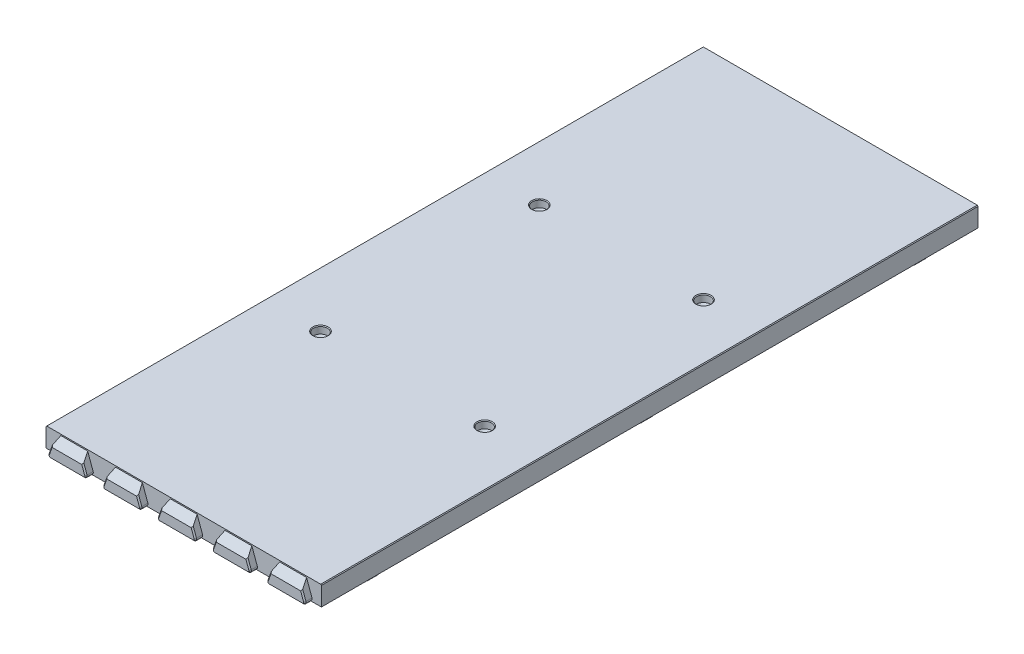
SolidWorks part; units mm, degrees
ref_plane "Front Plane" through (0, 0, 0) normal (0, 0, 1) x (1, 0, 0)
ref_plane "Top Plane" through (0, 0, 0) normal (0, 1, 0) x (1, 0, 0)
ref_plane "Right Plane" through (0, 0, 0) normal (1, 0, 0) x (0, 0, -1)
sketch "Sketch1" plane through (0, 0, 0) normal (0, 0, 1) x (1, 0, 0)
  line L0 (0, 0) -> (0, 8) construction
  line L1 (-56.625, 0) -> (0, 0) construction
  line L2 (-56.625, 0) -> (-56.625, 8)
  line L3 (-56.625, 8) -> (56.625, 8)
  line L5 (-56.625, 0) -> (-54.625, 0)
  line L6 (-54.625, 0) -> (-54.625, 6)
  line L7 (-54.625, 6) -> (54.625, 6)
  line L9 (54.625, 0) -> (54.625, 6)
  line L10 (56.625, 0) -> (54.625, 0)
  line L11 (56.625, 0) -> (56.625, 8)
  point P8 (0, 6)
  dimension "D2" = 6
  dimension "D1" = 56.625
  dimension "D3" = 2
  dimension "D4" = 2
extrude "Boss-Extrude1" add sketch "Sketch1" against normal blind 135
sketch "Sketch7" plane through (0, 0, 0) normal (0, 0, 1) x (1, 0, 0)
  line L2 (-54.625, 0) -> (54.625, 0)
  line L13 (-54.625, 0) -> (-54.625, 6)
  line L15 (-54.625, 6) -> (54.625, 6)
  line L16 (54.625, 0) -> (54.625, 6)
  line M3 (-54.625, 0) -> (-54.625, 6)
  line M4 (-54.625, 6) -> (54.625, 6)
  line M5 (54.625, 6) -> (54.625, 0)
extrude "Boss-Extrude7" add sketch "Sketch7" against normal blind 1 contours M4 M3 | M5 region at (0, 3, 0)
sketch "Sketch2" plane through (0, 0, 0) normal (0, 0, 1) x (1, 0, 0)
  line L14 (39.6618, 8) -> (36.75, 0)
  line L15 (56.625, 8) -> (-56.625, 8) construction
  line L16 (-56.625, 0) -> (56.625, 0) construction
  line L17 (36.75, 0) -> (53.25, 0)
  line L18 (39.6618, 8) -> (50.3382, 8)
  line L19 (-56.625, 0) -> (56.625, 0) construction
  line L21 (50.3382, 8) -> (53.25, 0)
  line L24 (33.75, 0) -> (33.75, 8) construction
  line L27 (17.1618, 8) -> (14.25, 0)
  line L28 (17.1618, 8) -> (27.8382, 8)
  line L29 (14.25, 0) -> (30.75, 0)
  line L30 (27.8382, 8) -> (30.75, 0)
  line L31 (-5.3382, 8) -> (-8.25, 0)
  line L32 (-5.3382, 8) -> (5.3382, 8)
  line L33 (-8.25, 0) -> (8.25, 0)
  line L34 (5.3382, 8) -> (8.25, 0)
  line L35 (-27.8382, 8) -> (-30.75, 0)
  line L36 (-27.8382, 8) -> (-17.1618, 8)
  line L37 (-30.75, 0) -> (-14.25, 0)
  line L38 (-17.1618, 8) -> (-14.25, 0)
  line L39 (39.6618, 8) -> (17.1618, 8) construction
  line L40 (56.25, 8) -> (56.25, 0) construction
  line L41 (56.625, 0) -> (56.625, 8) construction
  line L42 (-56.25, 8) -> (-56.25, 0) construction
  line L43 (-56.625, 8) -> (-56.625, 0) construction
  line L44 (-50.3382, 8) -> (-53.25, 0)
  line L45 (-50.3382, 8) -> (-39.6618, 8)
  line L46 (-53.25, 0) -> (-36.75, 0)
  line L47 (-39.6618, 8) -> (-36.75, 0)
  point P22 (45, 8)
  point P23 (22.5, 8)
  dimension "D1" = 70
  dimension "D2" = 0.375
  dimension "D3" = 3
  dimension "D4" = 3
  dimension "D5" = 70
  dimension "D7" = 22.5
  dimension "D8" = 22.5
  dimension "D9" = 0.375
  dimension "D10" = 25.5
  dimension "D11" = 8
  dimension "D6" = 5
extrude "Boss-Extrude4" add sketch "Sketch2" along normal blind 3
sketch "Sketch8" plane through (0, 0, 0) normal (0, -1, 0) x (1, 0, 0)
  line L0 (-56.625, -22.5) -> (56.625, -22.5) construction
  line L2 (56.625, -135) -> (56.625, 0) construction
  line L3 (-56.625, 0) -> (-53.25, 0) construction
  line L4 (-55.25, -24.9559) -> (-55.25, -20.0441)
  line L5 (-55.25, -20.0441) -> (-51.25, -21.5)
  line L6 (-51.25, -21.5) -> (-51.25, -23.5)
  line L7 (-55.25, -135) -> (-55.25, -132.5441)
  line L8 (-55.25, -132.5441) -> (-51.25, -134)
  line L9 (-51.25, -134) -> (-51.25, -135)
  line L10 (-54.625, -135) -> (54.625, -135) construction
  line L11 (-51.25, -135) -> (-55.25, -135)
  line L12 (-55.25, -24.9559) -> (-51.25, -23.5)
  line L13 (0, -135) -> (0, 0) construction
  line L23 (-56.625, -135) -> (-56.625, 0) construction
  line L24 (55.25, -24.9559) -> (51.25, -23.5)
  line L25 (51.25, -21.5) -> (51.25, -23.5)
  line L26 (55.25, -20.0441) -> (51.25, -21.5)
  line L27 (55.25, -24.9559) -> (55.25, -20.0441)
  line L28 (-56.625, -135) -> (-54.625, -135) construction
  line L29 (51.25, -135) -> (55.25, -135)
  line L30 (51.25, -134) -> (51.25, -135)
  line L31 (55.25, -132.5441) -> (51.25, -134)
  line L32 (55.25, -135) -> (55.25, -132.5441)
  point P19 (-51.25, -22.5)
  point P32 (51.25, -22.5)
  dimension "D1" = 22.5
  dimension "D3" = 70
  dimension "D4" = 4
  dimension "D5" = 1.375
  dimension "D6" = 4
  dimension "D7" = 70
  dimension "D8" = 1
  dimension "D9" = 1
extrude "Boss-Extrude8" add sketch "Sketch8" against normal up to next and the other way blind 2
chamfer "Chamfer4" distance 0.5 angle 45 14 edges at (-51.25, -2, -134.5) (-53.25, -2, -133.2721) (-55.25, -2, -133.7721) (-53.25, -2, -24.2279) (-51.25, -2, -22.5) (-53.25, -2, -20.7721) (51.25, -2, -22.5) (53.25, -2, -24.2279) (53.25, -2, -20.7721) (55.25, -2, -22.5) (51.25, -2, -134.5) (55.25, -2, -133.7721) (53.25, -2, -133.2721) (-55.25, -2, -22.5)
fillet "Fillet4" radius 1 10 edges at (53.25, 0, 1.5) (36.75, 0, 1.5) (30.75, 0, 1.5) (14.25, 0, 1.5) (8.25, 0, 1.5) (-8.25, 0, 1.5) (-14.25, 0, 1.5) (-30.75, 0, 1.5) (-36.75, 0, 1.5) (-53.25, 0, 1.5)
chamfer "Chamfer6" distance 0.5 angle 45 25 edges at (38.4501, 4.671, 3) (51.5499, 4.671, 3) (45, 0, 3) (-29.0499, 4.671, 3) (-22.5, 0, 3) (-15.9501, 4.671, 3) (-6.5499, 4.671, 3) (0, 0, 3) (6.5499, 4.671, 3) (15.9501, 4.671, 3) (29.0499, 4.671, 3) (22.5, 0, 3) (-51.5499, 4.671, 3) (-38.4501, 4.671, 3) (-45, 0, 3) (-52.641, 0.4264, 3) (-37.359, 0.4264, 3) (-30.141, 0.4264, 3) (-14.859, 0.4264, 3) (-7.641, 0.4264, 3) (7.641, 0.4264, 3) (14.859, 0.4264, 3) (30.141, 0.4264, 3) (37.359, 0.4264, 3) (52.641, 0.4264, 3)
fillet "Fillet2" radius 2 23 edges at (0, 6, -1) (-54.625, 3, -132.7716) (-52.9375, 6, -133.3858) (-51.25, 6, -134.5) (-54.625, 3, -1) (-52.9375, 6, -20.8858) (-54.625, 3, -20.2716) (-54.625, 6, -78.75) (-51.25, 6, -22.5) (-52.9375, 6, -24.1142) (-54.625, 3, -24.7284) (54.625, 6, -10.6358) (54.625, 3, -1) (-54.625, 6, -10.6358) (54.625, 3, -24.7284) (54.625, 3, -20.2716) (54.625, 3, -132.7716) (51.25, 6, -134.5) (52.9375, 6, -133.3858) (52.9375, 6, -20.8858) (51.25, 6, -22.5) (54.625, 6, -78.75) (52.9375, 6, -24.1142)
mirror "Mirror2" about plane through (0, 0, -135) normal (0, 0, 1) of "Fillet4", "Boss-Extrude1", "Boss-Extrude7", "Boss-Extrude4", "Boss-Extrude8", "Chamfer4", "Fillet2", "Chamfer6"
sketch "Sketch9" plane through (0, 0, 0) normal (0, 1, 0) x (1, 0, 0)
  line L16 (0, 135) -> (0, 0) construction
  line L17 (-56.625, 135) -> (56.625, 135) construction
  line L18 (-56.625, 137.9563) -> (-56.625, 132.0437) construction
  line L20 (56.625, 270) -> (56.625, 0) construction
  circle A0 centre (-33.75, 90) radius 5
  circle A4 centre (33.75, 90) radius 5
  circle A5 centre (33.75, 180) radius 5
  circle A6 centre (-33.75, 180) radius 5
  point P23 (0, 135)
  point P24 (0, 135)
  dimension "D3" = 10
  dimension "D1" = 33.75
  dimension "D2" = 45
extrude "Boss-Extrude9" add sketch "Sketch9" along normal up to next
fillet "Fillet3" radius 3 4 edges at (-33.75, 6, -95) (33.75, 6, -185) (-33.75, 6, -185) (33.75, 6, -95)
sketch "Sketch10" plane through (0, 0, 0) normal (0, 1, 0) x (1, 0, 0)
  circle A0 centre (-33.75, 180) radius 1.85
  circle A1 centre (-33.75, 90) radius 1.85
  circle A2 centre (33.75, 90) radius 1.85
  circle A3 centre (33.75, 180) radius 1.85
  dimension "D1" = 3.7
extrude "Cut-Extrude2" cut sketch "Sketch10" along normal through all
sketch "Sketch11" plane through (0, 8, 0) normal (0, 1, 0) x (1, 0, 0)
  circle A0 centre (-33.75, 180) radius 2.85
  circle A1 centre (33.75, 180) radius 2.85
  circle A2 centre (33.75, 90) radius 2.85
  circle A3 centre (-33.75, 90) radius 2.85
  dimension "D1" = 5.7
extrude "Cut-Extrude3" cut sketch "Sketch11" against normal blind 3
chamfer "Chamfer7" distance 1 angle 45 4 edges at (33.75, 5, -178.15) (-33.75, 5, -178.15) (33.75, 5, -88.15) (-33.75, 5, -88.15)
sketch "Sketch12" plane through (0, 0, 0) normal (1, 0, 0) x (0, 0, -1)
  line L0 (0, 7.5) -> (-3, 4.5)
  line L1 (-3, 1.171) -> (-3, 8) construction
  line L2 (-3, 4.5) -> (-3, 7.5)
  line L4 (135, 8) -> (135, 0) construction
  line L5 (270, 8) -> (0, 8) construction
  line L6 (270, 0) -> (0, 0) construction
  line L10 (0, 0) -> (0, 8) construction
  line L11 (-3, 7.5) -> (0, 7.5) construction
  line L12 (0, 7.5) -> (0, 8)
  line L13 (0, 8) -> (-3, 8)
  line L14 (-3, 8) -> (-3, 7.5)
  line L15 (273, 7.5) -> (270, 7.5) construction
  line L16 (273, 8) -> (273, 7.5)
  line L17 (270, 8) -> (273, 8)
  line L18 (270, 7.5) -> (270, 8)
  line L19 (273, 4.5) -> (273, 7.5)
  line L20 (270, 7.5) -> (273, 4.5)
  dimension "D1" = 0.5
  dimension "D2" = 3
  dimension "D3" = 45
extrude "Cut-Extrude4" cut sketch "Sketch12" against normal through all both and the other way through all
chamfer "Chamfer8" distance 0.3 angle 45 6 edges at (-56.625, 8, -135) (56.625, 8, -135) (33.75, 8, -87.15) (-33.75, 8, -87.15) (-33.75, 8, -177.15) (33.75, 8, -177.15)
